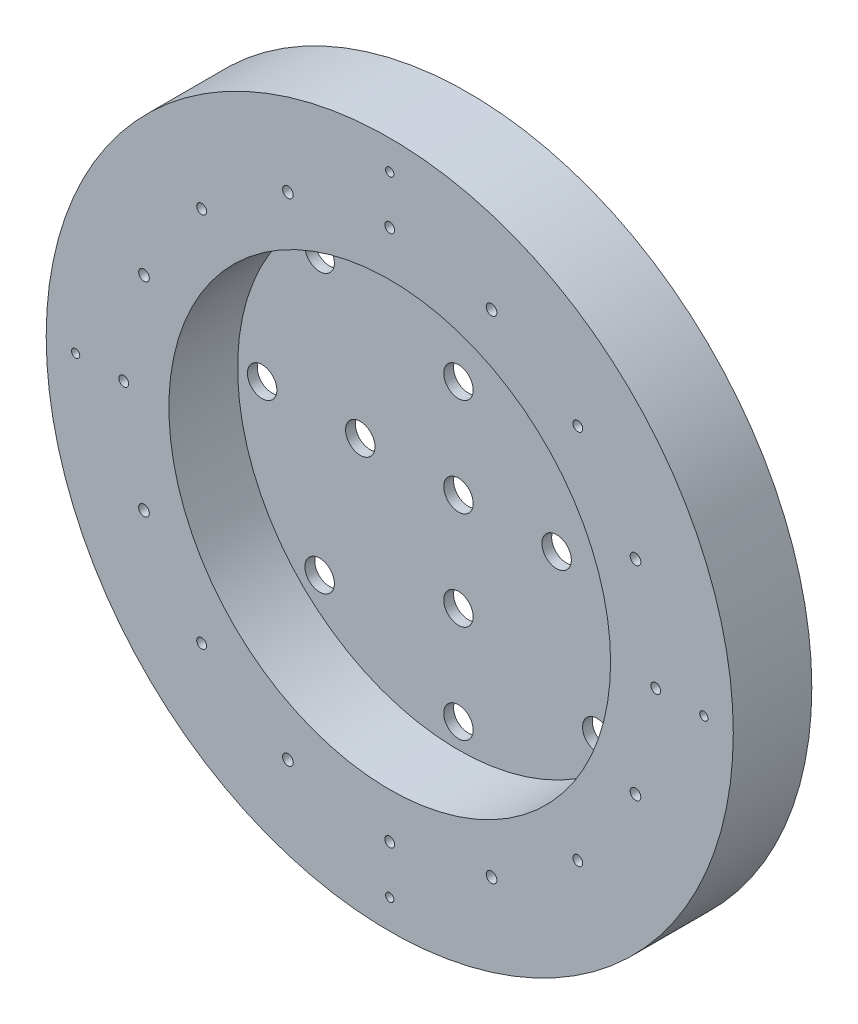
SolidWorks part; units mm, degrees
ref_plane "正面" through (0, 0, 0) normal (0, 0, 1) x (1, 0, 0)
ref_plane "平面" through (0, 0, 0) normal (0, 1, 0) x (1, 0, 0)
ref_plane "右側面" through (0, 0, 0) normal (1, 0, 0) x (0, 0, -1)
ref_axis "軸1" through (0, 0, -2) along (0, 0, 1)
sketch "ｽｹｯﾁ1" plane through (0, 0, 0) normal (0, 0, 1) x (1, 0, 0)
  circle A0 centre (0, 0) radius 175
  dimension "D1" = 350
extrude "ﾎﾞｽ - 押し出し1" add sketch "ｽｹｯﾁ1" along normal blind 40
sketch "ｽｹｯﾁ2" plane through (0, 0, 40) normal (0, 0, 1) x (1, 0, 0)
  circle A0 centre (0, 0) radius 112.5
  dimension "D1" = 225
extrude "ｶｯﾄ - 押し出し1" cut sketch "ｽｹｯﾁ2" against normal blind 35
hole_wizard "M12 すきま穴1" positions "ｽｹｯﾁ5" profile "ｽｹｯﾁ4" hole size "M12" standard "JIS" end condition through all
sketch "ｽｹｯﾁ5" plane through (0, 0, 5) normal (0, 0, 1) x (1, 0, 0)
  point P0 (0, 100)
  point P2 (0, 50)
  point P11 (70.7107, 70.7107)
  point P12 (100, 0)
  point P13 (70.7107, -70.7107)
  point P14 (0, -100)
  point P15 (-70.7107, -70.7107)
  point P16 (-100, 0)
  point P17 (-70.7107, 70.7107)
  point P18 (0, 0)
  point P23 (50, 0)
  point P24 (0, -50)
  point P25 (-50, 0)
  point P26 (0, 0)
  dimension "D1" = 100
  dimension "D2" = 50
  dimension "D3" = 8
  dimension "D4" = 4
sketch "ｽｹｯﾁ4" plane through (0, 100, 5) normal (1, 0, 0) x (0, -1, 0)
  line L0 (0, 0) -> (0, 5)
  line L1 (0, 5) -> (7.5, 5)
  line L2 (7.5, 5) -> (7.5, 0)
  line L5 (7.5, 0) -> (0, 0)
  line L11 (0, -6.35) -> (0, 107.95) construction
  dimension "通し穴の直径" = 15
  dimension "通し穴の深さ" = 5
hole_wizard "M6x1.0 ねじ穴1" positions "ｽｹｯﾁ7" profile "ｽｹｯﾁ6" tap size "M6x1.0" standard "JIS" end condition through all
sketch "ｽｹｯﾁ7" plane through (0, 0, 40) normal (0, 0, 1) x (1, 0, 0)
  point P0 (0, 135.5)
  point P8 (95.813, 95.813)
  point P9 (135.5, 0)
  point P10 (95.813, -95.813)
  point P11 (0, -135.5)
  point P12 (-95.813, -95.813)
  point P13 (-135.5, 0)
  point P14 (-95.813, 95.813)
  point P15 (0, 0)
  dimension "D1" = 135.5
  dimension "D2" = 8
sketch "ｽｹｯﾁ6" plane through (0, 135.5, 40) normal (1, 0, 0) x (0, -1, 0)
  line L0 (0, 0) -> (0, 40)
  line L1 (0, 40) -> (2.5, 40)
  line L2 (2.5, 40) -> (2.5, 0)
  line L5 (2.5, 0) -> (0, 0)
  line L11 (0, -6.35) -> (0, 107.95) construction
  dimension "次ｻｰﾌｪｽまでのねじ下穴ﾄﾞﾘﾙ直径" = 5
  dimension "次ｻｰﾌｪｽまでのねじ下穴ﾄﾞﾘﾙの深さ" = 40
cosmetic thread "穴のねじ山1" parameters "D2"=6
cosmetic thread "穴のねじ山2" parameters "D2"=6
cosmetic thread "穴のねじ山3" parameters "D2"=6
cosmetic thread "穴のねじ山4" parameters "D2"=6
cosmetic thread "穴のねじ山5" parameters "D2"=6
cosmetic thread "穴のねじ山6" parameters "D2"=6
cosmetic thread "穴のねじ山7" parameters "D2"=6
cosmetic thread "穴のねじ山8" parameters "D2"=6
sketch "ｽｹｯﾁ8" plane through (0, 0, 40) normal (0, 0, 1) x (1, 0, 0)
  line L0 (0, 166.9589) -> (0, 0) construction
  point P3 (51.8536, 125.1857)
  dimension "D1" = 22.5
  dimension "D2" = 135.5
hole_wizard "1/4-28 ねじ穴1" positions "ｽｹｯﾁ10" profile "ｽｹｯﾁ9" tap size "1/4-28" standard "Ansi Inch" end condition through all
sketch "ｽｹｯﾁ10" plane through (0, 0, 40) normal (0, 0, 1) x (1, 0, 0)
  point P0 (51.8536, 125.1857)
  point P7 (125.1857, 51.8536)
  point P8 (125.1857, -51.8536)
  point P9 (51.8536, -125.1857)
  point P10 (-51.8536, -125.1857)
  point P11 (-125.1857, -51.8536)
  point P12 (-125.1857, 51.8536)
  point P13 (-51.8536, 125.1857)
  point P14 (0, 0)
  dimension "D1" = 8
sketch "ｽｹｯﾁ9" plane through (51.8536, 125.1857, 40) normal (1, 0, 0) x (0, -1, 0)
  line L0 (0, 0) -> (0, 40)
  line L1 (0, 40) -> (2.7051, 40)
  line L2 (2.7051, 40) -> (2.7051, 0)
  line L5 (2.7051, 0) -> (0, 0)
  line L11 (0, -6.35) -> (0, 107.95) construction
  dimension "次ｻｰﾌｪｽまでのねじ下穴ﾄﾞﾘﾙ直径" = 5.4102
  dimension "次ｻｰﾌｪｽまでのねじ下穴ﾄﾞﾘﾙの深さ" = 40
cosmetic thread "穴のねじ山9" parameters "D2"=6.35
cosmetic thread "穴のねじ山10" parameters "D2"=6.35
cosmetic thread "穴のねじ山11" parameters "D2"=6.35
cosmetic thread "穴のねじ山12" parameters "D2"=6.35
cosmetic thread "穴のねじ山13" parameters "D2"=6.35
cosmetic thread "穴のねじ山14" parameters "D2"=6.35
cosmetic thread "穴のねじ山15" parameters "D2"=6.35
cosmetic thread "穴のねじ山16" parameters "D2"=6.35
hole_wizard "M5x0.8 ねじ穴1" positions "ｽｹｯﾁ13" profile "ｽｹｯﾁ12" tap size "M5x0.8" standard "JIS" end condition through all
sketch "ｽｹｯﾁ13" plane through (0, 0, 40) normal (0, 0, 1) x (1, 0, 0)
  point P0 (0, 160)
  point P9 (160, 0)
  point P10 (0, -160)
  point P11 (-160, 0)
  point P12 (0, 0)
  dimension "D1" = 160
  dimension "D2" = 4
sketch "ｽｹｯﾁ12" plane through (0, 160, 40) normal (1, 0, 0) x (0, -1, 0)
  line L0 (0, 0) -> (0, 40)
  line L1 (0, 40) -> (2.1, 40)
  line L2 (2.1, 40) -> (2.1, 0)
  line L5 (2.1, 0) -> (0, 0)
  line L11 (0, -6.35) -> (0, 107.95) construction
  dimension "次ｻｰﾌｪｽまでのねじ下穴ﾄﾞﾘﾙ直径" = 4.2
  dimension "次ｻｰﾌｪｽまでのねじ下穴ﾄﾞﾘﾙの深さ" = 40
cosmetic thread "穴のねじ山17" parameters "D2"=5
cosmetic thread "穴のねじ山18" parameters "D2"=5
cosmetic thread "穴のねじ山19" parameters "D2"=5
cosmetic thread "穴のねじ山20" parameters "D2"=5
